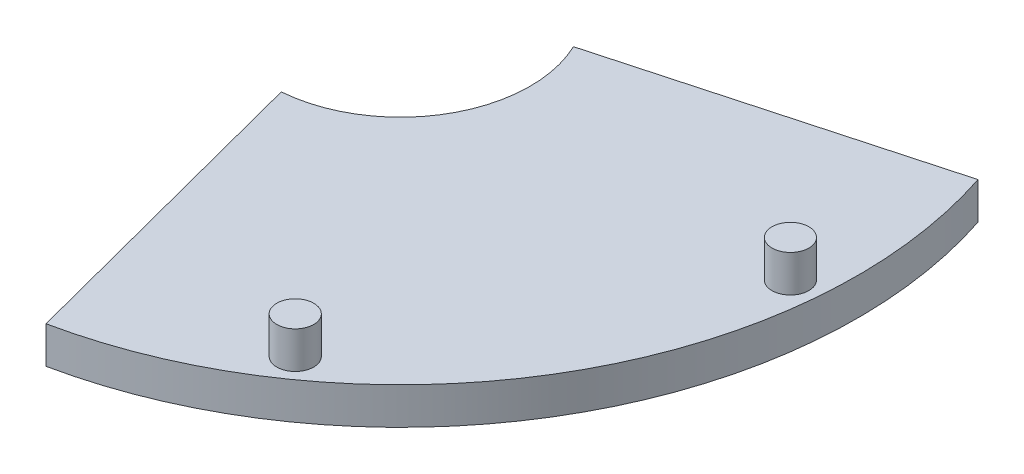
SolidWorks part; units mm, degrees
ref_plane "前视基准面" through (0, 0, 0) normal (0, 0, 1) x (1, 0, 0)
ref_plane "上视基准面" through (0, 0, 0) normal (0, 1, 0) x (1, 0, 0)
ref_plane "右视基准面" through (0, 0, 0) normal (1, 0, 0) x (0, 0, -1)
other "Configuration Table"
sketch "草图1" plane through (0, 0, 0) normal (0, 1, 0) x (1, 0, 0)
  line L0 (-96.6214, 38.3034) -> (-70.8184, 45.3915)
  line L1 (-105.3163, 23.2435) -> (-98.5532, -2.6467)
  arc A0 (-70.8184, 45.3915) -> (-98.5532, -2.6467) centre (-106.1496, 33.7646) cw
  arc A1 (-96.6214, 38.3034) -> (-105.3163, 23.2435) centre (-106.1496, 33.7646) cw
  circle A2 centre (-86.1186, 5.1838) radius 1.5
  circle A3 centre (-71.3731, 30.6958) radius 1.5
extrude "凸台-拉伸1" add sketch "草图1" along normal blind 3
sketch "草图2" plane through (0, 3, 0) normal (0, 1, 0) x (1, 0, 0)
  circle A0 centre (-71.3731, 30.6958) radius 1.5
  circle A1 centre (-86.1186, 5.1838) radius 1.5
extrude "凸台-拉伸2" add sketch "草图2" along normal blind 3 and the other way blind 3
